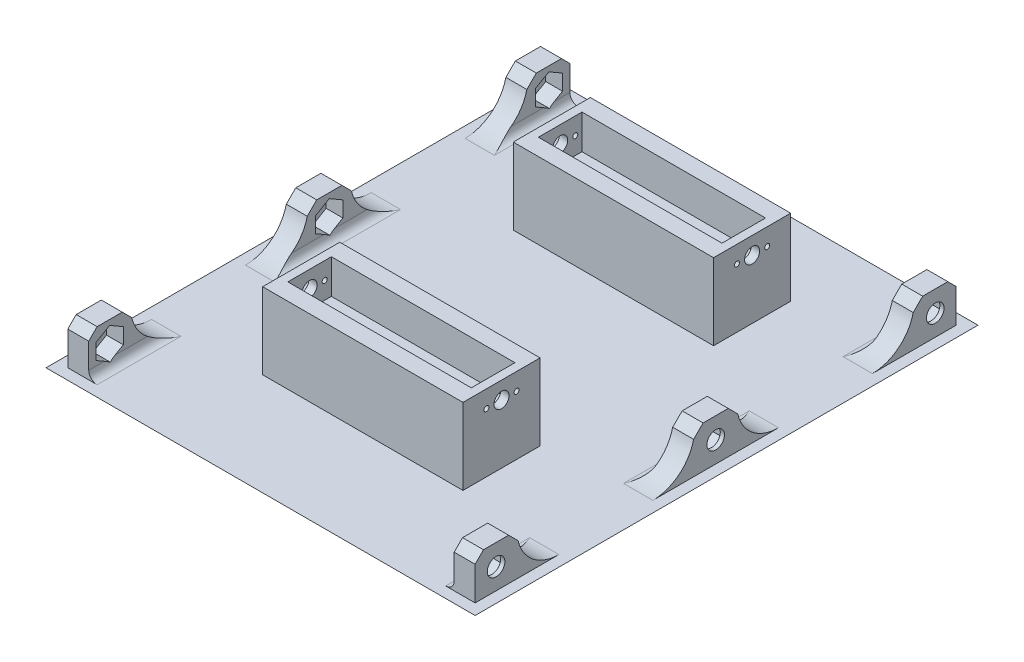
SolidWorks part; units mm, degrees
ref_plane "Front Plane" through (0, 0, 0) normal (0, 0, 1) x (1, 0, 0)
ref_plane "Top Plane" through (0, 0, 0) normal (0, 1, 0) x (1, 0, 0)
ref_plane "Right Plane" through (0, 0, 0) normal (1, 0, 0) x (0, 0, -1)
sketch "Sketch1" plane through (0, 0, 0) normal (0, 1, 0) x (1, 0, 0)
  line L1 (65.024, 76.2) -> (-65.024, 76.2)
  line L2 (65.024, 76.2) -> (65.024, -76.2)
  line L3 (65.024, -76.2) -> (-65.024, -76.2)
  line L4 (-65.024, 76.2) -> (-65.024, -76.2)
  line L5 (65.024, 76.2) -> (-65.024, -76.2) construction
  line L6 (65.024, -76.2) -> (-65.024, 76.2) construction
  point P0 (0, 0)
  dimension "D1" = 130.048
  dimension "D2" = 152.4
extrude "Boss-Extrude1" add sketch "Sketch1" along normal blind 2.54 contours L1 L4 L3 L2
chamfer "Chamfer1" distance 2.54 angle 45 4 edges at (0, 0, -76.2) (-65.024, 0, 0) (0, 0, 76.2) (65.024, 0, 0)
sketch "Sketch2" plane through (0, 2.54, 0) normal (0, 1, 0) x (1, 0, 0)
  line L1 (-27.813, 49.022) -> (27.813, 49.022)
  line L2 (-27.813, 49.022) -> (-27.813, 35.814)
  line L3 (-27.813, 35.814) -> (27.813, 35.814)
  line L4 (27.813, 49.022) -> (27.813, 35.814)
  line L5 (-27.813, 49.022) -> (27.813, 35.814) construction
  line L6 (-27.813, 35.814) -> (27.813, 49.022) construction
  line L7 (-27.813, -26.924) -> (27.813, -26.924)
  line L8 (-27.813, -26.924) -> (-27.813, -40.132)
  line L9 (-27.813, -40.132) -> (27.813, -40.132)
  line L10 (27.813, -26.924) -> (27.813, -40.132)
  line L11 (-27.813, -26.924) -> (27.813, -40.132) construction
  line L12 (-27.813, -40.132) -> (27.813, -26.924) construction
  line L13 (30.353, 54.102) -> (-30.353, 54.102)
  line L14 (30.353, 54.102) -> (30.353, 30.734)
  line L15 (30.353, 30.734) -> (-30.353, 30.734)
  line L16 (-30.353, 54.102) -> (-30.353, 30.734)
  line L17 (30.353, 54.102) -> (-30.353, 30.734) construction
  line L18 (30.353, 30.734) -> (-30.353, 54.102) construction
  line L19 (30.353, -45.212) -> (-30.353, -45.212)
  line L20 (30.353, -45.212) -> (30.353, -21.844)
  line L21 (30.353, -21.844) -> (-30.353, -21.844)
  line L22 (-30.353, -45.212) -> (-30.353, -21.844)
  line L23 (30.353, -45.212) -> (-30.353, -21.844) construction
  line L24 (30.353, -21.844) -> (-30.353, -45.212) construction
  line L26 (-65.024, -72.898) -> (65.024, -72.898) construction
  line L27 (-65.024, 76.2) -> (-65.024, -76.2) construction
  line L28 (65.024, 76.2) -> (65.024, -76.2) construction
  line L29 (65.024, -76.2) -> (-65.024, -76.2) construction
  point P0 (0, 42.418)
  point P5 (0, -33.528)
  point P10 (0, 42.418)
  point P16 (0, -33.528)
  dimension "D1" = 55.626
  dimension "D2" = 13.208
  dimension "D3" = 3.302
  dimension "D4" = 39.37
  dimension "D5" = 2.54
  dimension "D6" = 5.08
  dimension "D7" = 115.316
extrude "Boss-Extrude2" add sketch "Sketch2" along normal blind 23.114
extrude "Boss-Extrude3" add sketch "Sketch2<2>" along normal blind 12.7 contours L10 L7 L8 L9 | L4 L1 L2 L3 region at (0, 2.54, -42.418) region at (0, 2.54, 33.528)
sketch "Sketch2<2>" plane through (0, 2.54, 0) normal (0, 1, 0) x (1, 0, 0) same geometry as "Sketch2"
sketch "Sketch3" plane through (0, 0, 0) normal (1, 0, 0) x (0, 0, -1)
  line L0 (42.418, 25.654) -> (42.418, 15.24) construction
  line L1 (30.734, 25.654) -> (54.102, 25.654) construction
  line L2 (49.022, 15.24) -> (35.814, 15.24) construction
  line L3 (37.846, 20.447) -> (46.99, 20.447) construction
  line L4 (-21.844, 25.654) -> (30.734, 25.654) construction
  line L5 (4.445, 25.654) -> (4.445, 2.54) construction
  line L6 (76.2, 2.54) -> (-76.2, 2.54) construction
  line L7 (-28.956, 20.447) -> (-38.1, 20.447) construction
  line L8 (-33.528, 25.654) -> (-33.528, 15.24) construction
  circle A0 centre (42.418, 20.447) radius 2.286
  circle A1 centre (46.99, 20.447) radius 0.762
  circle A2 centre (37.846, 20.447) radius 0.762
  circle A3 centre (-28.956, 20.447) radius 0.762
  circle A4 centre (-38.1, 20.447) radius 0.762
  circle A5 centre (-33.528, 20.447) radius 2.286
  point P8 (42.418, 20.447)
  dimension "D1" = 1.524
  dimension "D2" = 4.572
  dimension "D3" = 7.62
extrude "Cut-Extrude1" cut sketch "Sketch3" against normal through all both and the other way through all
sketch "Sketch4" plane through (0, 2.54, 0) normal (0, 1, 0) x (1, 0, 0)
  line L0 (0, 76.2) -> (0, -76.2) construction
  line L1 (-61.722, 72.898) -> (-55.372, 72.898)
  line L2 (-61.722, 72.898) -> (-61.722, 60.198)
  line L3 (-61.722, 60.198) -> (-55.372, 60.198)
  line L4 (-55.372, 72.898) -> (-55.372, 60.198)
  line L5 (-61.722, 72.898) -> (-55.372, 60.198) construction
  line L6 (-61.722, 60.198) -> (-55.372, 72.898) construction
  line L7 (-61.722, 6.35) -> (-55.372, 6.35)
  line L8 (-61.722, 6.35) -> (-61.722, -6.35)
  line L9 (-61.722, -6.35) -> (-55.372, -6.35)
  line L10 (-55.372, 6.35) -> (-55.372, -6.35)
  line L11 (-61.722, 6.35) -> (-55.372, -6.35) construction
  line L12 (-61.722, -6.35) -> (-55.372, 6.35) construction
  line L13 (-61.722, -60.198) -> (-55.372, -60.198)
  line L14 (-61.722, -60.198) -> (-61.722, -72.898)
  line L15 (-61.722, -72.898) -> (-55.372, -72.898)
  line L16 (-55.372, -60.198) -> (-55.372, -72.898)
  line L17 (-61.722, -60.198) -> (-55.372, -72.898) construction
  line L18 (-61.722, -72.898) -> (-55.372, -60.198) construction
  line L19 (65.024, 76.2) -> (-65.024, 76.2) construction
  line L20 (65.024, -76.2) -> (-65.024, -76.2) construction
  line L22 (61.722, -72.898) -> (55.372, -60.198) construction
  line L23 (61.722, -60.198) -> (55.372, -72.898) construction
  line L24 (61.722, -6.35) -> (55.372, 6.35) construction
  line L25 (61.722, 6.35) -> (55.372, -6.35) construction
  line L26 (61.722, 60.198) -> (55.372, 72.898) construction
  line L27 (61.722, 72.898) -> (55.372, 60.198) construction
  line L28 (55.372, -60.198) -> (55.372, -72.898)
  line L29 (61.722, -72.898) -> (55.372, -72.898)
  line L30 (61.722, -60.198) -> (61.722, -72.898)
  line L31 (61.722, -60.198) -> (55.372, -60.198)
  line L32 (55.372, 6.35) -> (55.372, -6.35)
  line L33 (61.722, -6.35) -> (55.372, -6.35)
  line L34 (61.722, 6.35) -> (61.722, -6.35)
  line L35 (61.722, 6.35) -> (55.372, 6.35)
  line L36 (55.372, 72.898) -> (55.372, 60.198)
  line L37 (61.722, 60.198) -> (55.372, 60.198)
  line L38 (61.722, 72.898) -> (61.722, 60.198)
  line L39 (61.722, 72.898) -> (55.372, 72.898)
  line L40 (-58.547, 60.198) -> (-58.547, -60.198) construction
  point P4 (-58.547, 66.548)
  point P9 (-58.547, 0)
  point P14 (-58.547, -66.548)
  point P21 (-58.547, 0)
  point P38 (58.547, -66.548)
  point P39 (58.547, 0)
  point P40 (58.547, 66.548)
  dimension "D1" = 12.7
  dimension "D2" = 6.35
  dimension "D3" = 123.444
  dimension "D4" = 145.796
extrude "Boss-Extrude4" add sketch "Sketch4" along normal blind 12.7
sketch "Sketch5" plane through (0, 0, 0) normal (1, 0, 0) x (0, 0, -1)
  line L0 (0, 15.24) -> (0, 2.54) construction
  line L1 (-6.35, 15.24) -> (6.35, 15.24) construction
  line L2 (76.2, 2.54) -> (-76.2, 2.54) construction
  line L3 (66.548, 15.24) -> (66.548, 2.54) construction
  line L4 (0, 4.124) -> (4.1275, 6.507)
  line L5 (4.1275, 6.507) -> (4.1275, 11.273)
  line L6 (4.1275, 11.273) -> (0, 13.656)
  line L7 (0, 13.656) -> (-4.1275, 11.273)
  line L8 (-4.1275, 11.273) -> (-4.1275, 6.507)
  line L9 (-4.1275, 6.507) -> (0, 4.124)
  line L10 (60.198, 15.24) -> (72.898, 15.24) construction
  line L11 (60.198, 2.54) -> (72.898, 2.54) construction
  line L12 (-66.548, 15.24) -> (-66.548, 2.54) construction
  line L13 (-72.898, 15.24) -> (-60.198, 15.24) construction
  line L14 (-72.898, 2.54) -> (-60.198, 2.54) construction
  line L16 (-66.548, 4.124) -> (-62.4205, 6.507)
  line L17 (-62.4205, 6.507) -> (-62.4205, 11.273)
  line L18 (-62.4205, 11.273) -> (-66.548, 13.656)
  line L19 (-66.548, 13.656) -> (-70.6755, 11.273)
  line L20 (-70.6755, 11.273) -> (-70.6755, 6.507)
  line L21 (-70.6755, 6.507) -> (-66.548, 4.124)
  line L22 (66.548, 4.124) -> (70.6755, 6.507)
  line L23 (70.6755, 6.507) -> (70.6755, 11.273)
  line L24 (70.6755, 11.273) -> (66.548, 13.656)
  line L25 (66.548, 13.656) -> (62.4205, 11.273)
  line L26 (62.4205, 11.273) -> (62.4205, 6.507)
  line L27 (62.4205, 6.507) -> (66.548, 4.124)
  circle A0 centre (0, 8.89) radius 4.1275 construction
  circle A1 centre (0, 8.89) radius 2.667
  circle A2 centre (-66.548, 8.89) radius 4.1275 construction
  circle A3 centre (66.548, 8.89) radius 4.1275 construction
  circle A4 centre (-66.548, 8.89) radius 2.667
  circle A5 centre (66.548, 8.89) radius 2.667
  point P7 (-2.0637, 5.3155)
  dimension "D2" = 5.334
  dimension "D1" = 8.255
extrude "Cut-Extrude2" cut sketch "Sketch5" against normal through all both and the other way through all contours A4 | A1 | A5 region at (0, 8.89, 0) region at (0, 8.89, 66.548) region at (0, 8.89, -66.548)
extrude "Cut-Extrude3" cut sketch "Sketch5<3>" against normal offset from surface 1.27 and the other way offset from surface 1.27 up to face at (-61.722, 8.89, 63.881) other way up to face at (61.722, 8.89, 69.215)
sketch "Sketch5<3>" plane through (0, 0, 0) normal (1, 0, 0) x (0, 0, -1) same geometry as "Sketch5"
fillet "Fillet1" radius 12.7 8 edges at (58.547, 2.54, 60.198) (58.547, 2.54, 6.35) (58.547, 2.54, -6.35) (58.547, 2.54, -60.198) (-58.547, 2.54, 60.198) (-58.547, 2.54, 6.35) (-58.547, 2.54, -6.35) (-58.547, 2.54, -60.198)
fillet "Fillet2" radius 2.54 6 edges at (55.372, 2.54, 60.198) (-55.372, 2.54, 60.198) (-55.372, 2.54, 0) (55.372, 2.54, 0) (55.372, 2.54, -60.198) (-55.372, 2.54, -60.198)
chamfer "Chamfer2" distance 2.54 angle 45 12 edges at (58.547, 15.24, -72.898) (-58.547, 15.24, -72.898) (-58.547, 15.24, 72.898) (58.547, 15.24, 60.198) (58.547, 15.24, 72.898) (58.547, 15.24, 6.35) (58.547, 15.24, -6.35) (58.547, 15.24, -60.198) (-58.547, 15.24, -60.198) (-58.547, 15.24, -6.35) (-58.547, 15.24, 6.35) (-58.547, 15.24, 60.198)
